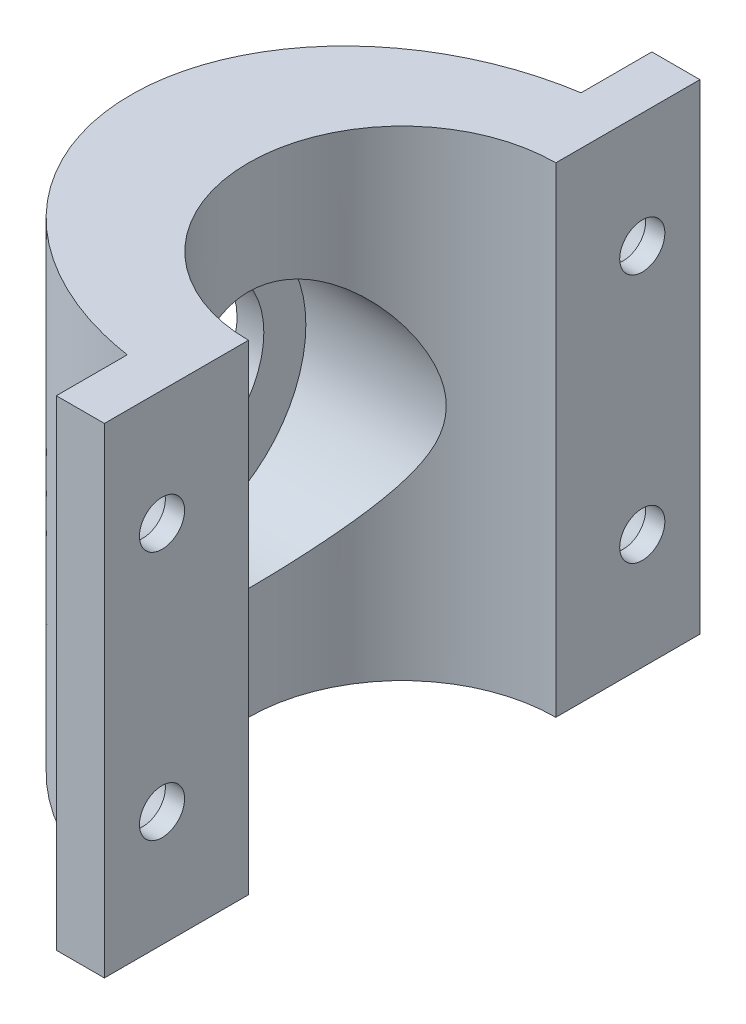
SolidWorks part; units mm, degrees
ref_plane "Front Plane" through (0, 0, 0) normal (0, 0, 1) x (1, 0, 0)
ref_plane "Top Plane" through (0, 0, 0) normal (0, 1, 0) x (1, 0, 0)
ref_plane "Right Plane" through (0, 0, 0) normal (1, 0, 0) x (0, 0, -1)
sketch "Sketch1" plane through (0, 0, 0) normal (0, 1, 0) x (1, 0, 0)
  line L1 (0, -16) -> (0, -31)
  line L2 (-5, -31) -> (0, -31)
  line L4 (0, 16) -> (0, 31)
  line L5 (0, 31) -> (-5, 31)
  line L6 (-5, 23.6211) -> (-5, 31)
  line L10 (-5, -23.6211) -> (-5, -31)
  arc A1 (0, 16) -> (0, -16) centre (0, 0) ccw
  ellipse E0 centre (0, 0) end of major axis (28.25, 0) minor radius 24 (-5, 23.6211) -> (-5, -23.6211) ccw
  dimension "D3" = 8
  dimension "D1" = 32
  dimension "D2" = 5
  dimension "D4" = 15
  dimension "D5" = 15
  dimension "D6" = 28.25
extrude "Boss-Extrude1" add sketch "Sketch1" along normal blind 50
sketch "Sketch2" plane through (-5, 0, 0) normal (-1, 0, 0) x (0, 0, 1)
  line L0 (-31, 50) -> (-23.6211, 50) construction
  line L20 (-31, 0) -> (-23.6211, 0) construction
  line L21 (0, -15.5375) -> (0, 15.5375) construction
  line L35 (-31, 50) -> (-31, 0) construction
  circle A0 centre (-25, 38) radius 4.375
  circle A1 centre (-25, 12) radius 4.375
  circle A2 centre (-25, 38) radius 2.35
  circle A3 centre (-25, 12) radius 2.35
  circle A4 centre (25, 12) radius 2.35
  circle A5 centre (25, 12) radius 4.375
  circle A6 centre (25, 38) radius 2.35
  circle A7 centre (25, 38) radius 4.375
  line M47 (-23.6211, 0) -> (-23.6211, 50)
  dimension "D1" = 8.75
  dimension "D2" = 8.75
  dimension "D5" = 4.7
  dimension "D6" = 4.7
  dimension "D7" = 6
  dimension "D3" = 12
  dimension "D4" = 12
extrude "Cut-Extrude1" cut sketch "Sketch2" against normal blind 10 contours A2 | A4 | A6 | A3
extrude "Cut-Extrude6" cut sketch "Sketch2<8>" along normal blind 20
sketch "Sketch2<8>" plane through (-5, 0, 0) normal (-1, 0, 0) x (0, 0, 1) same geometry as "Sketch2"
extrude "Cut-Extrude7" cut sketch "Sketch2<9>" along normal blind 23 contours A2 M47 | A2 M47 | A4 | A3 | A6 region at (-5, 38, -25.3112) region at (-5, 38, -23.2248) region at (-5, 12, 25)
sketch "Sketch2<9>" plane through (-5, 0, 0) normal (-1, 0, 0) x (0, 0, 1) same geometry as "Sketch2"
extrude "Boss-Extrude2" add sketch "Sketch2<13>" against normal blind 3 contours A2 M47 | A2 M47 | A3 M47 | A3 M47 | A6 | A4 region at (-5, 38, -25.3112) region at (-5, 38, -23.2248) region at (-5, 12, -25.3112) region at (-5, 12, -23.2248) region at (-5, 12, 25) region at (-5, 38, 25)
sketch "Sketch2<13>" plane through (-5, 0, 0) normal (-1, 0, 0) x (0, 0, 1) same geometry as "Sketch2"
extrude "Cut-Extrude2" cut sketch "Sketch2<3>" against normal blind 0.01
sketch "Sketch2<3>" plane through (-5, 0, 0) normal (-1, 0, 0) x (0, 0, 1) same geometry as "Sketch2"
loft "Cut-Loft7" cut body kept at (0, 0, 16) section edge at (-2, 38, -22.65) section edge at (-4.99, 38, -20.625) start constraint default connector at (-2, 38.4345, -22.6905) connector at (-4.99, 40.3023, -21.2798)
loft "Cut-Loft8" cut body kept at (0, 0, 16) section edge at (-2, 12, -22.65) section edge at (-4.99, 12, -20.625) connector at (-2, 13.6783, -23.3551) connector at (-4.99, 15.3463, -22.1817)
loft "Cut-Loft9" cut body kept at (0, 0, 16) section edge at (-4.99, 38, 20.625) section edge at (-2, 38, 27.35) connector at (-4.99, 41.9679, 26.8429) connector at (-2, 40.0388, 26.1686)
loft "Cut-Loft10" cut body kept at (0, 0, 16) section edge at (-4.99, 12, 20.625) section face at (-2, 12, 27.35) connector at (-4.99, 16.3712, 25.1814) connector at (-2, 14.3497, 24.9631)
sketch "Sketch9" plane through (0, 0, 0) normal (1, 0, 0) x (0, 0, -1)
  line L1 (-16, 50) -> (-16, 0) construction
  circle A0 centre (0, 25) radius 13.375
  circle A1 centre (0, 26.5) radius 9
  point P8 (-16, 25)
  dimension "D1" = 26.75
  dimension "D2" = 18
  dimension "D3" = 1.5
extrude "Cut-Extrude4" cut sketch "Sketch9" against normal blind 23.4
extrude "Cut-Extrude5" cut sketch "Sketch9<2>" against normal blind 30 contours A1 region at (0, 26.5, 0)
sketch "Sketch9<2>" plane through (0, 0, 0) normal (1, 0, 0) x (0, 0, -1) same geometry as "Sketch9"
